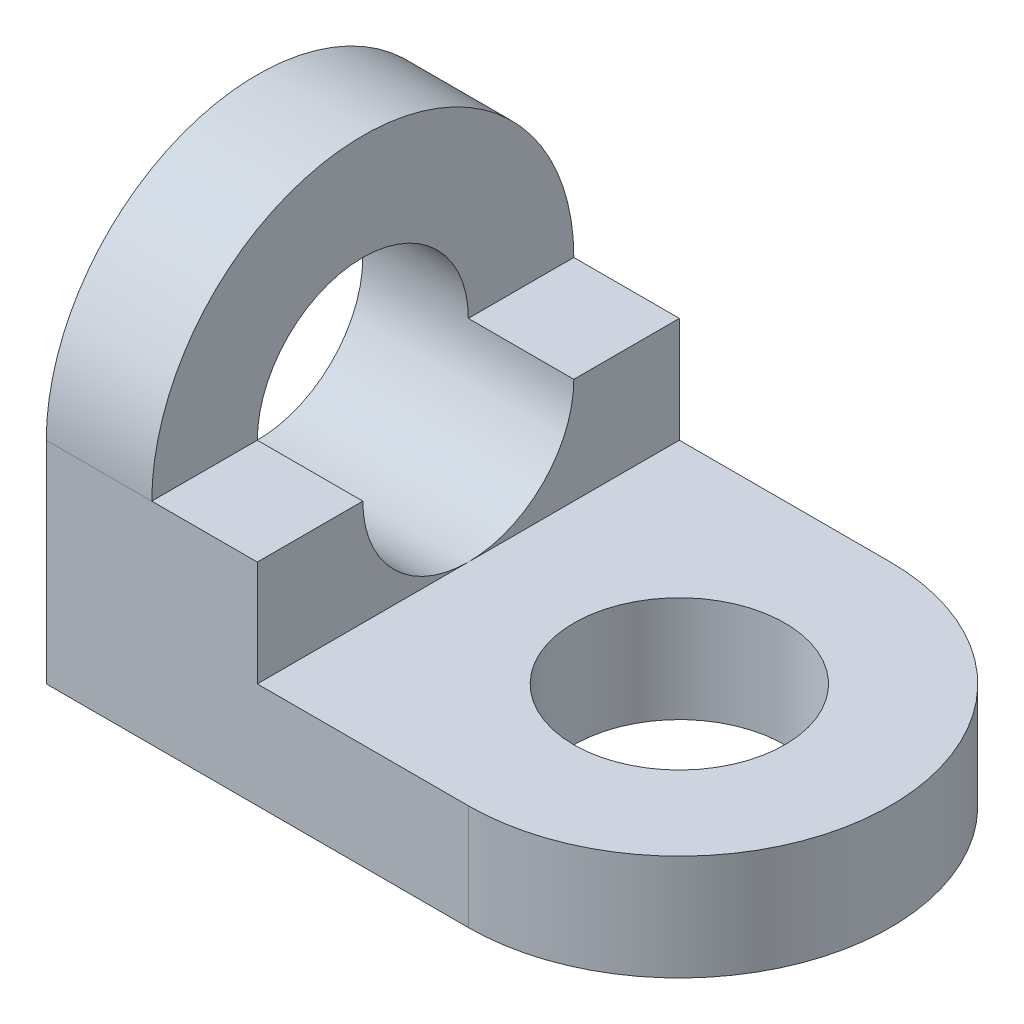
SolidWorks part; units mm, degrees
ref_plane "前基準面" through (0, 0, 0) normal (0, 0, 1) x (1, 0, 0)
ref_plane "上基準面" through (0, 0, 0) normal (0, 1, 0) x (1, 0, 0)
ref_plane "右基準面" through (0, 0, 0) normal (1, 0, 0) x (0, 0, -1)
sketch "草圖1" plane through (0, 0, 0) normal (0, 1, 0) x (1, 0, 0)
  line L0 (0, 0) -> (20, 0) construction
  line L1 (20, 10) -> (0, 10)
  line L2 (0, 10) -> (0, -10)
  line L3 (0, -10) -> (20, -10)
  circle A0 centre (20, 0) radius 5
  arc A1 (20, -10) -> (20, 10) centre (20, 0) ccw
  dimension "D1" = 10
  dimension "D2" = 20
  dimension "D3" = 20
extrude "填料-伸長1" add sketch "草圖1" along normal blind 5
sketch "草圖2" plane through (0, 0, 0) normal (1, 0, 0) x (0, 0, -1)
  line L0 (0, 0) -> (0, 13.6598) construction
  line L1 (-10, 10) -> (4.4405, 10) construction
  line L2 (-10, 10) -> (-10, 0)
  line L3 (-10, 5) -> (10, 5)
  line L4 (10, 5) -> (10, 10)
  line L5 (-10, 0) -> (10, 0)
  line L6 (10, 0) -> (10, 10)
  line L7 (-5, 10) -> (-10, 10)
  line L8 (5, 10) -> (10, 10)
  circle A0 centre (0, 10) radius 5
  arc A1 (10, 10) -> (-10, 10) centre (0, 10) ccw
  dimension "D2" = 10
  dimension "D3" = 20
  dimension "D1" = 10
extrude "填料-伸長3" add sketch "草圖2" along normal blind 5 contours L5 L6 L3 L2 | A1 L2 L5 L6 | A0 region at (0, 2.5, 0)
extrude "填料-伸長4" add sketch "草圖2<4>" along normal blind 10 contours L5 L6 L3 L2 | A0 L7 L2 L3 | A0 L3 L4 L8 region at (0, 7.2556, 6.861) region at (0, 2.5, 0) region at (0, 7.2556, -6.861)
sketch "草圖2<4>" plane through (0, 0, 0) normal (1, 0, 0) x (0, 0, -1) same geometry as "草圖2"
